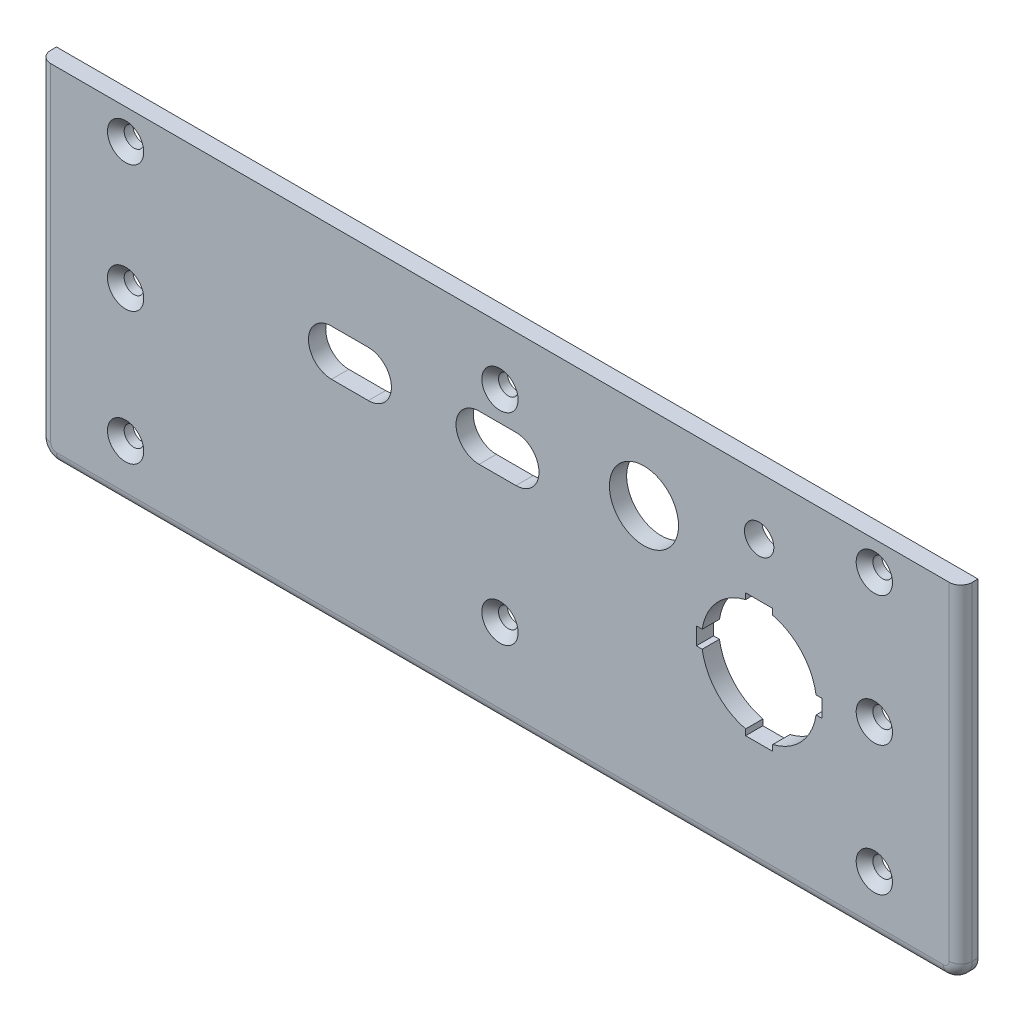
SolidWorks part; units mm, degrees
ref_plane "Front Plane" through (0, 0, 0) normal (0, 0, 1) x (1, 0, 0)
ref_plane "Top Plane" through (0, 0, 0) normal (0, 1, 0) x (1, 0, 0)
ref_plane "Right Plane" through (0, 0, 0) normal (1, 0, 0) x (0, 0, -1)
sketch "Sketch11" plane through (0, 0, 0) normal (0, 0, 1) x (1, 0, 0)
  line L0 (-44.8869, 31.5) -> (-45.8972, 31.5)
  line L1 (-45.8972, 31.5) -> (-45.8972, 28.5)
  line L2 (-45.8972, 28.5) -> (-44.8869, 28.5)
  line L3 (-35, 30) -> (-45.8972, 30) construction
  line L4 (-37.35, 20.28) -> (-37.35, 19.254)
  line L5 (-37.35, 19.254) -> (-32.65, 19.254)
  line L6 (-32.65, 19.254) -> (-32.65, 20.28)
  line L7 (-35, 30) -> (-35, 19.254) construction
  line L8 (-32.65, 40.746) -> (-32.65, 39.72)
  line L9 (-37.35, 40.746) -> (-32.65, 40.746)
  line L10 (-37.35, 39.72) -> (-37.35, 40.746)
  line L11 (-35, 18.7315) -> (-35, 30) construction
  line L12 (-25.1131, 31.5) -> (-24.1028, 31.5)
  line L13 (-24.1028, 31.5) -> (-24.1028, 28.5)
  line L14 (-24.1028, 28.5) -> (-25.1131, 28.5)
  line L15 (-35, 50) -> (-35, 30) construction
  line L17 (0, 0) -> (-160, 0)
  line L18 (0, 0) -> (0, 60)
  line L19 (0, 60) -> (-160, 60)
  line L20 (-160, 0) -> (-160, 60)
  line L21 (-83.6273, 40.9303) -> (-77.2273, 40.9303) construction
  line L22 (-83.6273, 44.9303) -> (-77.2273, 44.9303)
  line L23 (-83.6273, 36.9303) -> (-77.2273, 36.9303)
  line L24 (-109.2528, 40.9) -> (-102.8528, 40.9) construction
  line L25 (-109.2528, 44.9) -> (-102.8528, 44.9)
  line L26 (-109.2528, 36.9) -> (-102.8528, 36.9)
  arc A0 (-44.8869, 28.5) -> (-37.35, 20.28) centre (-35, 30) ccw
  circle A1 centre (-35, 30) radius 11 construction
  arc A2 (-32.65, 20.28) -> (-25.1131, 28.5) centre (-35, 30) ccw
  arc A3 (-37.35, 39.72) -> (-44.8869, 31.5) centre (-35, 30) ccw
  arc A4 (-25.1131, 31.5) -> (-32.65, 39.72) centre (-35, 30) ccw
  circle A5 centre (-35, 50) radius 2.55
  circle A6 centre (-55, 45) radius 6
  arc A7 (-102.3028, 40.9) -> (-102.8528, 41.45) centre (-102.8528, 40.9) ccw construction
  arc A8 (-109.2528, 41.45) -> (-109.8028, 40.9) centre (-109.2528, 40.9) ccw construction
  arc A9 (-76.6773, 40.9303) -> (-77.2273, 41.4803) centre (-77.2273, 40.9303) ccw construction
  arc A10 (-83.6273, 41.4803) -> (-84.1773, 40.9303) centre (-83.6273, 40.9303) ccw construction
  arc A11 (-102.3028, 40.9) -> (-102.8528, 41.45) centre (-102.8528, 40.9) ccw construction
  arc A12 (-109.2528, 41.45) -> (-109.8028, 40.9) centre (-109.2528, 40.9) ccw construction
  arc A13 (-76.6773, 40.9303) -> (-77.2273, 41.4803) centre (-77.2273, 40.9303) ccw construction
  arc A14 (-83.6273, 41.4803) -> (-84.1773, 40.9303) centre (-83.6273, 40.9303) ccw construction
  arc A15 (-83.6273, 44.9303) -> (-83.6273, 36.9303) centre (-83.6273, 40.9303) ccw
  arc A16 (-77.2273, 36.9303) -> (-77.2273, 44.9303) centre (-77.2273, 40.9303) ccw
  arc A17 (-109.2528, 44.9) -> (-109.2528, 36.9) centre (-109.2528, 40.9) ccw
  arc A18 (-102.8528, 36.9) -> (-102.8528, 44.9) centre (-102.8528, 40.9) ccw
  point P42 (-80.4273, 40.9303)
  point P47 (-106.0528, 40.9)
  point P52 (-55.6358, 44.1126)
  point P53 (-59.8033, 43.8931)
  dimension "D1" = 20
  dimension "D4" = 22
  dimension "D5" = 5.1
  dimension "D11" = 12
  dimension "D6" = 20
  dimension "D2" = 3
  dimension "D3" = 4.7
  dimension "D7" = 160
  dimension "D8" = 35
  dimension "D9" = 30
  dimension "D10" = 60
  dimension "D12" = 20
  dimension "D13" = 8
  dimension "D14" = 15
extrude "Boss-Extrude1" add sketch "Sketch11" along normal blind 3 contours L20 L17 L18 L19 A5 A4 L12 L13 L14 A2 L6 L5 L4 A0 L2 L1 L0 A3 L10 L9 L8 region at (-81.7686, 29.5166, 0)
fillet "Fillet1" radius 2 3 edges at (-80, 0, 3) (-160, 30, 3) (0, 30, 3)
fillet "Fillet3" radius 3 4 edges at (-0.5858, 0.5858, 2.4142) (-159.4142, 0.5858, 2.4142) (-160, 0, 0.5) (0, 0, 0.5)
sketch "Sketch12" plane through (0, 0, 3) normal (0, 0, 1) x (1, 0, 0)
  line L1 (-80, 50) -> (-80, 60) construction
  line L2 (-2, 60) -> (-158, 60) construction
  circle A0 centre (-145, 9.7613) radius 3 construction
  circle A1 centre (-145, 32.7387) radius 3 construction
  circle A2 centre (-145, 54.7613) radius 3 construction
  circle A3 centre (-15, 10) radius 3 construction
  circle A4 centre (-15, 32.5) radius 3 construction
  circle A5 centre (-15, 55) radius 3 construction
  circle A6 centre (-145, 9.7613) radius 3
  circle A7 centre (-145, 32.7387) radius 3
  circle A8 centre (-145, 54.7613) radius 3
  circle A9 centre (-15, 10) radius 3
  circle A10 centre (-15, 32.5) radius 3
  circle A11 centre (-15, 55) radius 3
  circle A12 centre (-80, 50) radius 3
  circle A13 centre (-80, 15) radius 3
  circle A14 centre (-80, 50) radius 3 construction
  circle A15 centre (-80, 15) radius 3 construction
hole_wizard "CSK for M3 Flat Head Machine Screw1" positions "3DSketch1" profile "Sketch13" countersink size "M3" standard "ANSI Metric" end condition through all
sketch3d "3DSketch1"
  point P0 (-145, 54.7613, 3)
  point P3 (-145, 32.7387, 3)
  point P6 (-145, 9.7613, 3)
  point P9 (-15, 10, 3)
  point P12 (-15, 32.5, 3)
  point P15 (-15, 55, 3)
  point P18 (-80, 50, 3)
  point P21 (-80, 15, 3)
sketch "Sketch13" plane through (-145, 54.7613, 3) normal (1, 0, 0) x (0, -1, 0)
  line L0 (0, 0) -> (0, 3)
  line L1 (0, 3) -> (1.7, 3)
  line L2 (1.7, 3) -> (1.7, 1.45)
  line L3 (1.7, 1.45) -> (3.15, 0)
  line L5 (3.15, 0) -> (0, 0)
  line L6 (-1.7, 1.45) -> (-3.15, 0) construction
  line L11 (0, -6.35) -> (0, 107.95) construction
  dimension "Thru Hole Dia." = 3.4
  dimension "Thru Hole Depth" = 3
  dimension "Near C'Sink Dia." = 6.3
  dimension "Near C'Sink Angle" = 90
